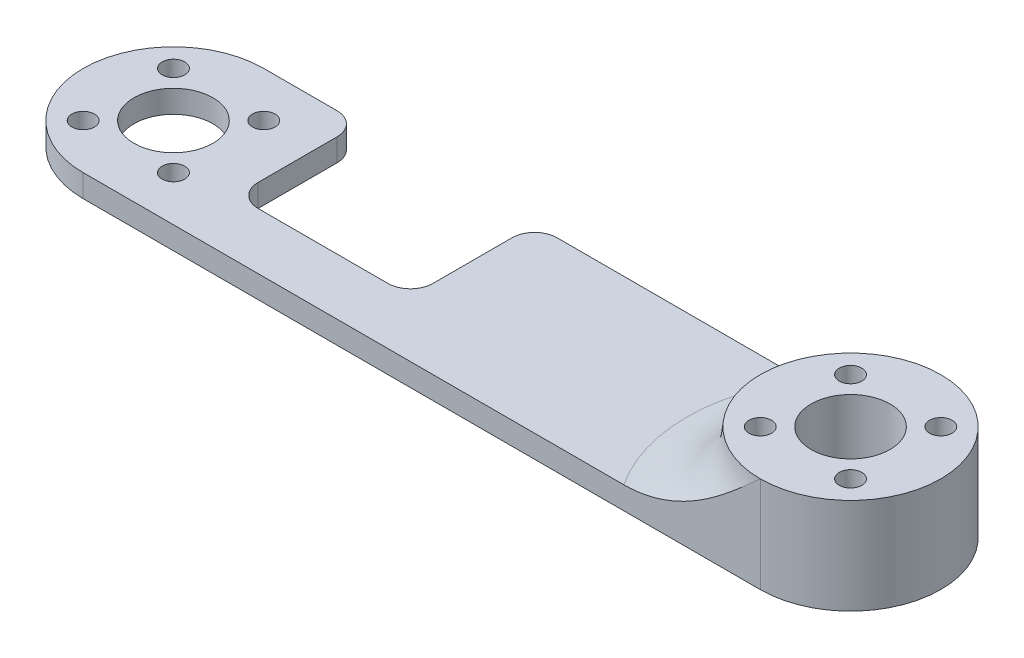
SolidWorks part; units mm, degrees
ref_plane "Front Plane" through (0, 0, 0) normal (0, 0, 1) x (1, 0, 0)
ref_plane "Top Plane" through (0, 0, 0) normal (0, 1, 0) x (1, 0, 0)
ref_plane "Right Plane" through (0, 0, 0) normal (1, 0, 0) x (0, 0, -1)
sketch "Sketch1" plane through (0, 0, 0) normal (0, 1, 0) x (1, 0, 0)
  line L0 (-60, 0) -> (60, 0) construction
  line L1 (-60, 16) -> (-43, 16)
  line L2 (-60, -16) -> (-43, -16)
  line L3 (-43, 6) -> (-43, -6)
  line L4 (-68, -8) -> (-52, -8) construction
  line L5 (-68, -8) -> (-68, 8) construction
  line L6 (-68, 8) -> (-52, 8) construction
  line L7 (-52, -8) -> (-52, 8) construction
  line L8 (-60, 8) -> (-60, -8) construction
  line L9 (-68, 0) -> (-52, 0) construction
  line L10 (52, -8) -> (68, -8) construction
  line L11 (52, -8) -> (52, 8) construction
  line L12 (52, 8) -> (68, 8) construction
  line L13 (68, -8) -> (68, 8) construction
  line L14 (60, 8) -> (60, -8) construction
  line L15 (52, 0) -> (68, 0) construction
  line L17 (-12, 6) -> (-12, -6)
  line L18 (4, -16) -> (60, -16)
  line L19 (-43, -16) -> (4, -16)
  line L20 (-43, -6) -> (-12, -6)
  line L21 (-43, 16) -> (-43, 6)
  line L22 (-12, 16) -> (-12, 6)
  line L23 (-12, 16) -> (60, 16)
  arc A0 (-60, 16) -> (-60, -16) centre (-60, 0) ccw
  arc A1 (60, -16) -> (60, 16) centre (60, 0) ccw
  circle A2 centre (-52, 8) radius 2
  circle A3 centre (-52, -8) radius 2
  circle A4 centre (-68, -8) radius 2
  circle A5 centre (-68, 8) radius 2
  circle A6 centre (52, 8) radius 2
  circle A7 centre (68, 8) radius 2
  circle A8 centre (68, -8) radius 2
  circle A9 centre (52, -8) radius 2
  circle A10 centre (-60, 0) radius 7
  circle A11 centre (60, 0) radius 7
  point P2 (0, 0)
  point P8 (-60, 0)
  point P12 (60, 0)
  dimension "D2" = 16
  dimension "D3" = 4
  dimension "D6" = 14
  dimension "D7" = 14
  dimension "D1" = 120
  dimension "D4" = 16
  dimension "D5" = 16
  dimension "D9" = 17
  dimension "D10" = 48
  dimension "D11" = 10
extrude "Boss-Extrude1" add sketch "Sketch1" along normal blind 4
fillet "Fillet1" radius 4 4 edges at (-43, 2, 6) (-12, 2, 6) (-12, 2, -16) (-43, 2, -16)
sketch "Sketch2" plane through (0, 4, 0) normal (0, 1, 0) x (1, 0, 0)
  circle A0 centre (60, 0) radius 16
  circle A1 centre (60, 0) radius 7
  circle A2 centre (52, 8) radius 2
  circle A3 centre (68, 8) radius 2
  circle A4 centre (52, -8) radius 2
  circle A5 centre (52, -8) radius 2 construction
  circle A6 centre (68, -8) radius 2
  point P18 (52, 8)
extrude "Boss-Extrude2" add sketch "Sketch2" along normal blind 13
fillet "Fillet2" radius 13 1 edges at (44, 4, 0)
